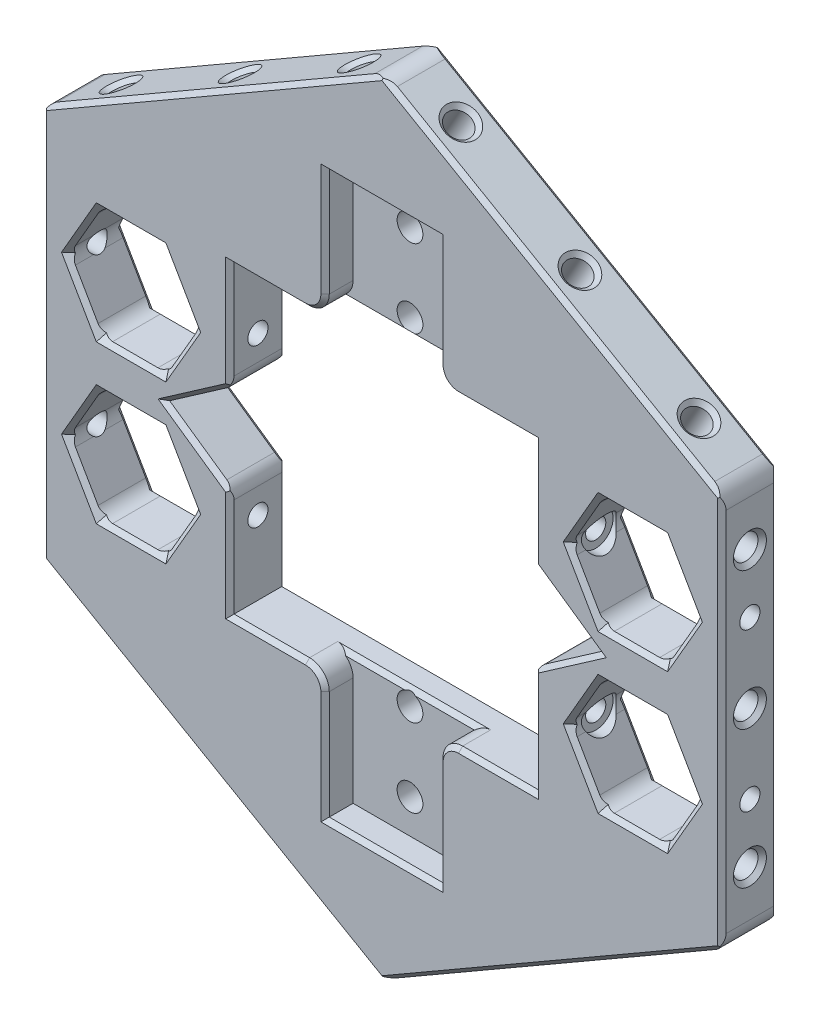
SolidWorks part; units mm, degrees
ref_plane "Front" through (0, 0, 0) normal (0, 0, 1) x (1, 0, 0)
ref_plane "Top" through (0, 0, 0) normal (0, 1, 0) x (1, 0, 0)
ref_plane "Right" through (0, 0, 0) normal (1, 0, 0) x (0, 0, -1)
sketch "Skizze1" plane through (0, 0, 0) normal (0, 0, 1) x (1, 0, 0)
  line L0 (0, 0) -> (0, 101.0458) construction
  line L5 (0, 50) -> (0, -50) construction
  line L6 (0, 0) -> (82.5372, 0) construction
  line L7 (0, 70) -> (60.6218, 35)
  line L8 (60.6218, 35) -> (60.6218, -35)
  line L9 (0, -70) -> (60.6218, -35)
  line L10 (0, -70) -> (-60.6218, -35)
  line L11 (-60.6218, 35) -> (-60.6218, -35)
  line L12 (0, 70) -> (-60.6218, 35)
  line L13 (27.05, 24.05) -> (27.05, -24.05) construction
  line L14 (-24.05, 27.05) -> (-10, 27.05) construction
  line L15 (-10.15, 27.2) -> (-27.125, 27.2)
  line L16 (-24.05, -27.05) -> (-10, -27.05) construction
  line L17 (24.05, -27.05) -> (27.05, -27.05) construction
  line L18 (27.05, -27.05) -> (27.05, -24.05) construction
  line L19 (27.05, 24.05) -> (27.05, 27.05) construction
  line L20 (27.05, 27.05) -> (24.05, 27.05) construction
  line L21 (-27.05, -24.05) -> (-27.05, 24.05) construction
  line L22 (-27.05, 24.05) -> (-27.05, 27.05) construction
  line L23 (-27.05, 27.05) -> (-24.05, 27.05) construction
  line L24 (-24.05, -27.05) -> (-27.05, -27.05) construction
  line L25 (-27.05, -27.05) -> (-27.05, -24.05) construction
  line L26 (10, 50) -> (10, 27.05) construction
  line L27 (10, 50) -> (-10, 50) construction
  line L28 (-10, 50) -> (-10, 27.05) construction
  line L29 (10, 27.05) -> (24.05, 27.05) construction
  line L30 (10, -27.05) -> (10, -50) construction
  line L31 (10, -50) -> (-10, -50) construction
  line L32 (-10, -50) -> (-10, -27.05) construction
  line L33 (10, -27.05) -> (24.05, -27.05) construction
  line L34 (-27.125, 27.2) -> (-27.125, 8)
  line L35 (-27.125, -27.2) -> (-10.15, -27.2)
  line L36 (-10.15, -27.2) -> (-10.15, -50.075)
  line L37 (-10.15, -50.075) -> (10.15, -50.075)
  line L38 (10.15, -50.075) -> (10.15, -27.2)
  line L39 (10.15, -27.2) -> (27.2, -27.2)
  line L40 (27.2, -27.2) -> (27.2, -8)
  line L41 (27.2, 27.2) -> (10.15, 27.2)
  line L42 (10.15, 27.2) -> (10.15, 50.075)
  line L43 (10.15, 50.075) -> (-10.15, 50.075)
  line L44 (-10.15, 50.075) -> (-10.15, 27.2)
  line L45 (27.2, 8) -> (38.7, 0)
  line L47 (27.2, 8) -> (27.2, 27.2)
  line L48 (27.2, -8) -> (38.7, 0)
  line L49 (0, 0) -> (-49.3387, 0) construction
  line L50 (-27.125, 8) -> (-38.625, 0)
  line L51 (-27.125, -8) -> (-38.625, 0)
  line L52 (-27.125, -8) -> (-27.125, -27.2)
  point P0 (0, 0)
  point P11 (60.6218, 0)
  dimension "D1" = 120
  dimension "D2" = 140
  dimension "D3" = 0.15
  dimension "D4" = 0.15
  dimension "D5" = 0.15
  dimension "D6" = 0.15
  dimension "D7" = 0.15
  dimension "D8" = 0.15
  dimension "D9" = 0.15
  dimension "D10" = 0.15
  dimension "D11" = 11.5
  dimension "D12" = 16
  dimension "D13" = 16
  dimension "D14" = 11.5
extrude "Aufsatz-Linear austragen1" add sketch "Skizze1" along normal blind 10
sketch "Skizze2" plane through (0, 0, 0) normal (0, 0, -1) x (-1, 0, 0)
  line L0 (0, 0) -> (52.0812, 0) construction
  line L1 (-10.15, 50.075) -> (10.15, 50.075)
  line L2 (-10.15, 50.075) -> (-10.15, 27.2)
  line L3 (-10.15, 27.2) -> (10.15, 27.2)
  line L4 (10.15, 50.075) -> (10.15, 27.2)
  line L5 (10.15, -50.075) -> (10.15, -27.2)
  line L6 (-10.15, -27.2) -> (10.15, -27.2)
  line L7 (-10.15, -50.075) -> (-10.15, -27.2)
  line L8 (-10.15, -50.075) -> (10.15, -50.075)
extrude "Aufsatz-Linear austragen2" add sketch "Skizze2" against normal blind 5
sketch "Skizze3" plane through (0, 0, 5) normal (0, 0, 1) x (1, 0, 0)
  circle A0 centre (0, 44) radius 2.3
  circle A1 centre (0, 30.05) radius 2.3
  circle A2 centre (0, -30.05) radius 2.3
  circle A3 centre (0, -44) radius 2.3
  dimension "D1" = 4.6
  dimension "D2" = 4.6
  dimension "D3" = 4.6
  dimension "D4" = 4.6
extrude "Schnitt-Linear austragen1" cut sketch "Skizze3" against normal through all
sketch "Skizze4" plane through (0, 0, 0) normal (0, 0, -1) x (-1, 0, 0)
  line L0 (-25.5409, 11.675) -> (-25.5409, 16.425) construction
  line L1 (-26.3, 11.675) -> (-20.05, 11.675) construction
  line L2 (-20.05, 16.425) -> (-26.3, 16.425) construction
  line L3 (-25.5409, 14.05) -> (-61.8124, 14.05) construction
  line L4 (-33.2, 14.05) -> (-33.2, 35.3851) construction
  line L6 (-44.747, 14.05) -> (-44.747, 21.7137) construction
  line L7 (-33.2, 14.05) -> (-38.9735, 24.05)
  line L8 (-38.9735, 24.05) -> (-50.5205, 24.05)
  line L9 (-56.294, 14.05) -> (-50.5205, 24.05)
  line L10 (-56.294, 14.05) -> (-50.5205, 4.05)
  line L11 (-33.2, 14.05) -> (-38.9735, 4.05)
  line L12 (-38.9735, 4.05) -> (-50.5205, 4.05)
  line L13 (0, 0) -> (0, 63.5416) construction
  line L14 (0, 0) -> (-74.0305, 0) construction
  line L15 (-56.294, -14.05) -> (-50.5205, -24.05)
  line L16 (-38.9735, -24.05) -> (-50.5205, -24.05)
  line L17 (-33.2, -14.05) -> (-38.9735, -24.05)
  line L18 (-33.2, -14.05) -> (-38.9735, -4.05)
  line L19 (-38.9735, -4.05) -> (-50.5205, -4.05)
  line L20 (-56.294, -14.05) -> (-50.5205, -4.05)
  line L21 (56.294, -14.05) -> (50.5205, -4.05)
  line L22 (38.9735, -4.05) -> (50.5205, -4.05)
  line L23 (33.2, -14.05) -> (38.9735, -4.05)
  line L24 (33.2, -14.05) -> (38.9735, -24.05)
  line L25 (38.9735, -24.05) -> (50.5205, -24.05)
  line L26 (56.294, -14.05) -> (50.5205, -24.05)
  line L27 (56.294, 14.05) -> (50.5205, 24.05)
  line L28 (38.9735, 24.05) -> (50.5205, 24.05)
  line L29 (33.2, 14.05) -> (38.9735, 24.05)
  line L30 (33.2, 14.05) -> (38.9735, 4.05)
  line L31 (38.9735, 4.05) -> (50.5205, 4.05)
  line L32 (56.294, 14.05) -> (50.5205, 4.05)
  line L33 (-27.2, -27.2) -> (-27.2, -8) construction
  point P19 (-44.747, 24.05)
  dimension "D1" = 6
  dimension "D2" = 120
  dimension "D3" = 20
extrude "Schnitt-Linear austragen2" cut sketch "Skizze4" against normal through all
ref_plane "Ebene1" through (-33.125, 0, 0) normal (1, 0, 0) x (0, 0, -1)
sketch "Skizze5" plane through (-33.125, 0, 0) normal (1, 0, 0) x (0, 0, -1)
  line L0 (-10, 14.05) -> (0, 14.05) construction
  line L1 (-10, -14.05) -> (0, -14.05) construction
  circle A0 centre (-5, 14.05) radius 1.8
  circle A1 centre (-5, -14.05) radius 1.8
  dimension "D1" = 3.6
  dimension "D2" = 3.6
extrude "Schnitt-Linear austragen5" cut sketch "Skizze5" along normal blind 20 and the other way blind 30
sketch "Skizze6" plane through (-33.125, 0, 0) normal (1, 0, 0) x (0, 0, -1)
  circle A0 centre (-5, 14.05) radius 3.1
  circle A1 centre (-5, -14.05) radius 3.1
  dimension "D1" = 6.2
extrude "Schnitt-Linear austragen6" cut sketch "Skizze6" against normal blind 10
mirror "Spiegeln1" about plane through (0, 0, 0) normal (1, 0, 0) of "Schnitt-Linear austragen6", "Schnitt-Linear austragen5"
sketch "Skizze7" plane through (60.6218, 0, 0) normal (1, 0, 0) x (0, 0, -1)
  line L0 (-5, 14.05) -> (-5, 35) construction
  line L3 (-10, 35) -> (0, 35) construction
  line L4 (0, 0) -> (-10, 0) construction
  line L5 (0, -35) -> (0, 35) construction
  line L6 (-10, -35) -> (-10, 35) construction
  circle A0 centre (-5, 24.525) radius 2.2
  circle A1 centre (-5, 0) radius 2.2
  circle A3 centre (-5, -24.525) radius 2.2
  dimension "D1" = 4.4
extrude "Schnitt-Linear austragen7" cut sketch "Skizze7" against normal blind 8
ref_plane "Ebene2" through (0, 0, 0) normal (-0.5, 0.866, 0) x (0.866, 0.5, 0)
mirror "Spiegeln6" about plane through (0, 0, 0) normal (-0.5, 0.866, 0) of "Schnitt-Linear austragen7"
mirror "Spiegeln7" about plane through (0, 0, 0) normal (0, 1, 0) of "Spiegeln6"
mirror "Spiegeln8" about plane through (0, 0, 0) normal (1, 0, 0) of "Spiegeln7", "Spiegeln6"
chamfer "Fase2" distance 0.75 angle 45 36 edges at (60.6218, -24.525, 7.2) (60.6218, 0, 2.8) (60.6218, 24.525, 2.8) (51.5502, -40.2375, 2.8) (47.5502, -33.3093, 2.8) (30.3109, -52.5, 2.8) (26.3109, -45.5718, 2.8) (9.0716, -64.7625, 7.2) (5.0716, -57.8343, 7.2) (-9.0716, -64.7625, 7.2) (-5.0716, -57.8343, 7.2) (-30.3109, -52.5, 2.8) (-26.3109, -45.5718, 2.8) (-51.5502, -40.2375, 2.8) (-47.5502, -33.3093, 2.8) (-60.6218, -24.525, 2.8) (-52.6218, -24.525, 2.8) (-60.6218, 0, 2.8) (-52.6218, 0, 2.8) (-60.6218, 24.525, 7.2) (-52.6218, 24.525, 7.2) (-51.5502, 40.2375, 2.8) (-47.5502, 33.3093, 2.8) (-30.3109, 52.5, 2.8) (-26.3109, 45.5718, 2.8) (-9.0716, 64.7625, 7.2) (-5.0716, 57.8343, 7.2) (9.0716, 64.7625, 7.2) (5.0716, 57.8343, 7.2) (30.3109, 52.5, 2.8) (26.3109, 45.5718, 2.8) (51.5502, 40.2375, 2.8) (47.5502, 33.3093, 2.8) (52.6218, 24.525, 2.8) (52.6218, 0, 2.8) (52.6218, -24.525, 7.2)
fillet "Verrundung4" radius 3.5 4 edges at (-10.15, 27.2, 7.5) (10.15, 27.2, 7.5) (10.15, -27.2, 7.5) (-10.15, -27.2, 7.5)
chamfer "Fase3" distance 0.75 angle 45 98 edges at (-60.6218, 0, 0) (-30.3109, -52.5, 0) (30.3109, -52.5, 0) (60.6218, 0, 0) (30.3109, 52.5, 0) (-30.3109, 52.5, 0) (2.3, -44, 0) (2.3, -30.05, 0) (2.3, 30.05, 0) (2.3, 44, 0) (44.747, 24.05, 0) (53.4073, 19.05, 0) (53.4073, 9.05, 0) (44.747, 4.05, 0) (36.0868, 9.05, 0) (36.0868, 19.05, 0) (44.747, -24.05, 0) (36.0868, -19.05, 0) (36.0868, -9.05, 0) (44.747, -4.05, 0) (53.4073, -9.05, 0) (53.4073, -19.05, 0) (-44.747, -4.05, 0) (-36.0868, -9.05, 0) (-36.0868, -19.05, 0) (-44.747, -24.05, 0) (-53.4073, -19.05, 0) (-53.4073, -9.05, 0) (-44.747, 24.05, 0) (-36.0868, 19.05, 0) (-36.0868, 9.05, 0) (-44.747, 4.05, 0) (-53.4073, 9.05, 0) (-53.4073, 19.05, 0) (30.3109, 52.5, 10) (60.6218, 0, 10) (30.3109, -52.5, 10) (-30.3109, -52.5, 10) (-60.6218, 0, 10) (-30.3109, 52.5, 10) (44.747, 4.05, 10) (53.4073, 9.05, 10) (53.4073, 19.05, 10) (44.747, 24.05, 10) (36.0868, 19.05, 10) (36.0868, 9.05, 10) (44.747, -4.05, 10) (36.0868, -9.05, 10) (36.0868, -19.05, 10) (44.747, -24.05, 10) (53.4073, -19.05, 10) (53.4073, -9.05, 10) (-44.747, -24.05, 10) (-36.0868, -19.05, 10) (-36.0868, -9.05, 10) (-44.747, -4.05, 10) (-53.4073, -9.05, 10) (-53.4073, -19.05, 10) (-44.747, 4.05, 10) (-36.0868, 9.05, 10) (-36.0868, 19.05, 10) (-44.747, 24.05, 10) (-53.4073, 19.05, 10) (-53.4073, 9.05, 10) (0, -27.2, 5) (0, 27.2, 5) (0.0375, -27.2, 0) (-27.125, 17.6, 0) (0.0375, 27.2, 0) (27.2, -17.6, 0) (-27.125, 17.6, 10) (-10.15, -40.3875, 10) (0, -50.075, 10) (10.15, -40.3875, 10) (20.425, -27.2, 10) (27.2, -17.6, 10) (10.15, 40.3875, 10) (0, 50.075, 10) (-10.15, 40.3875, 10) (-20.3875, 27.2, 10) (32.95, 4, 0) (27.2, 17.6, 0) (32.95, 4, 10) (27.2, 17.6, 10) (32.95, -4, 0) (32.95, -4, 10) (-27.125, -17.6, 0) (-32.875, -4, 0) (-32.875, 4, 0) (-32.875, 4, 10) (-32.875, -4, 10) (-27.125, -17.6, 10) (-20.3875, -27.2, 10) (-11.1751, -28.2251, 10) (11.1751, -28.2251, 10) (20.425, 27.2, 10) (11.1751, 28.2251, 10) (-11.1751, 28.2251, 10)
fillet "Verrundung1" radius 4 6 edges at (60.6218, -35, 5) (60.6218, 35, 5) (0, 70, 5) (-60.6218, 35, 5) (-60.6218, -35, 5) (0, -70, 5)
fillet "Verrundung2" radius 3 32 edges at (-50.5205, -24.05, 5) (-38.9735, -24.05, 5) (-33.2, -14.05, 8.675) (-33.2, -14.05, 1.325) (-38.9735, -4.05, 5) (-50.5205, -4.05, 5) (-56.294, -14.05, 8.025) (-56.294, -14.05, 1.975) (-56.294, 14.05, 8.025) (-56.294, 14.05, 1.975) (-50.5205, 4.05, 5) (-38.9735, 4.05, 5) (-33.2, 14.05, 8.675) (-33.2, 14.05, 1.325) (-38.9735, 24.05, 5) (-50.5205, 24.05, 5) (38.9735, 24.05, 5) (50.5205, 24.05, 5) (56.294, 14.05, 8.025) (56.294, 14.05, 1.975) (50.5205, 4.05, 5) (38.9735, 4.05, 5) (33.2, 14.05, 8.675) (33.2, 14.05, 1.325) (33.2, -14.05, 8.675) (33.2, -14.05, 1.325) (38.9735, -4.05, 5) (50.5205, -4.05, 5) (56.294, -14.05, 8.025) (56.294, -14.05, 1.975) (50.5205, -24.05, 5) (38.9735, -24.05, 5)
fillet "Verrundung3" radius 3 4 edges at (27.2, -8, 5) (27.2, 8, 5) (-27.125, -8, 5) (-27.125, 8, 5)
